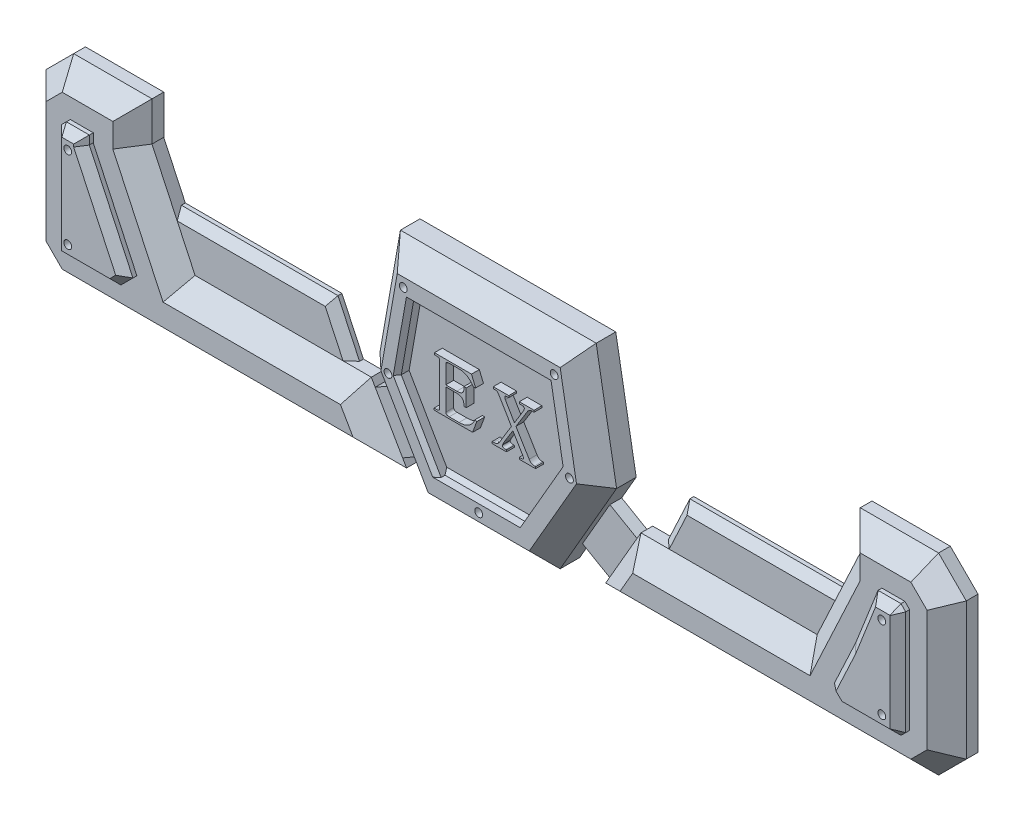
SolidWorks part; units mm, degrees
ref_plane "前视基准面" through (0, 0, 0) normal (0, 0, 1) x (1, 0, 0)
ref_plane "上视基准面" through (0, 0, 0) normal (0, 1, 0) x (1, 0, 0)
ref_plane "右视基准面" through (0, 0, 0) normal (1, 0, 0) x (0, 0, -1)
other "Configuration Table"
sketch "草图2" plane through (0, 0, 0) normal (0, 0, 1) x (1, 0, 0)
  line L0 (-21.0107, -24.9665) -> (10.5794, -24.9665)
  line L5 (10.5794, -24.9665) -> (24.9938, 0)
  line L6 (24.9938, 0) -> (19.7844, 29.5442)
  line L7 (19.7844, 29.5442) -> (-30.2156, 29.5442)
  line L8 (-30.2156, 29.5442) -> (-35.4251, 0)
  line L9 (-35.4251, 0) -> (-21.0107, -24.9665)
  dimension "D1" = 50
  dimension "D2" = 100
  dimension "D3" = 100
  dimension "D4" = 30
  dimension "D5" = 30
  dimension "D6" = 140
  dimension "D7" = 140
extrude "凸台-拉伸2" add sketch "草图2" along normal blind 10
chamfer "倒角1" distance 5 angle 45 6 edges at (-32.8203, 14.7721, 10) (-5.2156, 29.5442, 10) (22.3891, 14.7721, 10) (17.7866, -12.4832, 10) (-5.2156, -24.9665, 10) (-28.2179, -12.4832, 10)
sketch "草图4" plane through (0, 0, 10) normal (0, 0, 1) x (1, 0, 0)
  line L18 (-22.6637, 20.5442) -> (-25.993, 1.6631)
  line L19 (-25.993, 1.6631) -> (-15.8145, -15.9665)
  line L20 (-15.8145, -15.9665) -> (5.3833, -15.9665)
  line L21 (5.3833, -15.9665) -> (15.5617, 1.6631)
  line L22 (15.5617, 1.6631) -> (12.2325, 20.5442)
  line L23 (12.2325, 20.5442) -> (-22.6637, 20.5442)
  line L24 (-22.6637, 20.5442) -> (-25.993, 1.6631)
  line L25 (-25.993, 1.6631) -> (-15.8145, -15.9665)
  line L26 (-15.8145, -15.9665) -> (5.3833, -15.9665)
  line L27 (5.3833, -15.9665) -> (15.5617, 1.6631)
  line L28 (15.5617, 1.6631) -> (12.2325, 20.5442)
  line L29 (12.2325, 20.5442) -> (-22.6637, 20.5442)
  dimension "D1" = 4
extrude "切除-拉伸1" cut sketch "草图4" against normal blind 3
sketch "草图5" plane through (0, 0, 7) normal (0, 0, 1) x (1, 0, 0)
  text T0 "EX" font "宋体" height in points 42
extrude "凸台-拉伸3" add sketch "草图5" along normal blind 2
sketch "草图6" plane through (0, 0, 0) normal (0, 0, 1) x (1, 0, 0)
  line L1 (-35.4251, 0) -> (-21.0107, -24.9665) construction
  line L3 (-38.6461, -10.4211) -> (-31.7179, -6.4211)
  line L4 (-31.7179, -6.4211) -> (-24.7179, -18.5454)
  line L5 (-31.6461, -22.5454) -> (-38.6461, -10.4211)
  line L6 (-31.6461, -22.5454) -> (-24.7179, -18.5454)
  line L7 (-5.2156, 24.5442) -> (-5.2156, -15.9665) construction
  line L8 (15.5889, 24.5442) -> (-26.0201, 24.5442) construction
  line L9 (-15.8145, -15.9665) -> (5.3833, -15.9665) construction
  line L10 (-38.6461, -10.4211) -> (-31.7179, -6.4211)
  line L11 (-31.6461, -22.5454) -> (-24.7179, -18.5454)
  line L12 (-38.6461, -10.4211) -> (-31.7179, -6.4211)
  line L13 (-31.6461, -22.5454) -> (-24.7179, -18.5454)
  line L14 (-38.6461, -10.4211) -> (-31.7179, -6.4211)
  line L15 (-31.6461, -22.5454) -> (-24.7179, -18.5454)
  line L16 (-38.6461, -10.4211) -> (-31.7179, -6.4211)
  line L17 (-31.6461, -22.5454) -> (-24.7179, -18.5454)
  line L18 (-38.6461, -10.4211) -> (-31.7179, -6.4211)
  line L19 (-31.6461, -22.5454) -> (-24.7179, -18.5454)
  line L20 (-38.6461, -10.4211) -> (-31.7179, -6.4211)
  line L21 (-31.6461, -22.5454) -> (-24.7179, -18.5454)
  line L22 (-38.6461, -10.4211) -> (-31.7179, -6.4211)
  line L23 (-31.6461, -22.5454) -> (-24.7179, -18.5454)
  line L24 (-39.6457, -8.6896) -> (-38.6461, -10.4211)
  line L25 (-30.6461, -24.2775) -> (-31.6461, -22.5454)
  line L26 (-39.6457, -8.6896) -> (-84.6457, -8.6896)
  line L27 (-84.6457, -8.6896) -> (-95.6461, 14.8647)
  line L28 (-95.6461, 14.8647) -> (-95.6461, 24.8647)
  line L29 (-95.6461, 24.8647) -> (-115.6461, 24.8647)
  line L30 (-115.6461, 24.8647) -> (-122.7171, 17.7936)
  line L31 (-122.7171, 17.7936) -> (-122.7171, -17.2064)
  line L32 (-122.7171, -17.2064) -> (-115.6461, -24.2775)
  line L33 (-115.6461, -24.2775) -> (-30.6461, -24.2775)
  line L34 (-90.1459, 3.0875) -> (-50.1459, 3.0875)
  line L35 (-50.1459, 3.0875) -> (-44.6457, -8.6896)
  line L36 (39.7147, 3.0875) -> (34.2145, -8.6896)
  line L37 (79.7147, 3.0875) -> (39.7147, 3.0875)
  line L38 (105.2148, -24.2775) -> (20.2148, -24.2775)
  line L39 (112.2859, -17.2064) -> (105.2148, -24.2775)
  line L40 (112.2859, 17.7936) -> (112.2859, -17.2064)
  line L41 (105.2148, 24.8647) -> (112.2859, 17.7936)
  line L42 (85.2148, 24.8647) -> (105.2148, 24.8647)
  line L43 (85.2148, 14.8647) -> (85.2148, 24.8647)
  line L44 (74.2145, -8.6896) -> (85.2148, 14.8647)
  line L45 (29.2145, -8.6896) -> (74.2145, -8.6896)
  line L46 (20.2148, -24.2775) -> (21.2148, -22.5454)
  line L47 (29.2145, -8.6896) -> (28.2148, -10.4211)
  line L48 (21.2148, -22.5454) -> (14.2866, -18.5454)
  line L49 (28.2148, -10.4211) -> (21.2866, -6.4211)
  line L50 (21.2148, -22.5454) -> (14.2866, -18.5454)
  line L51 (28.2148, -10.4211) -> (21.2866, -6.4211)
  line L52 (21.2148, -22.5454) -> (14.2866, -18.5454)
  line L53 (28.2148, -10.4211) -> (21.2866, -6.4211)
  line L54 (21.2148, -22.5454) -> (14.2866, -18.5454)
  line L55 (28.2148, -10.4211) -> (21.2866, -6.4211)
  line L56 (21.2148, -22.5454) -> (14.2866, -18.5454)
  line L57 (28.2148, -10.4211) -> (21.2866, -6.4211)
  line L58 (21.2148, -22.5454) -> (14.2866, -18.5454)
  line L59 (28.2148, -10.4211) -> (21.2866, -6.4211)
  line L60 (21.2148, -22.5454) -> (14.2866, -18.5454)
  line L61 (28.2148, -10.4211) -> (21.2866, -6.4211)
  line L62 (21.2148, -22.5454) -> (14.2866, -18.5454)
  line L63 (21.2148, -22.5454) -> (28.2148, -10.4211)
  line L64 (21.2866, -6.4211) -> (14.2866, -18.5454)
  line L65 (28.2148, -10.4211) -> (21.2866, -6.4211)
  line L66 (-21.0107, -24.9665) -> (-35.4251, 0) construction
  point P40 (0, 0)
  dimension "D1" = 45
  dimension "D2" = 10
  dimension "D3" = 20
  dimension "D4" = 14
  dimension "D5" = 85
  dimension "D6" = 8
  dimension "D7" = 2
  dimension "D8" = 10
  dimension "D9" = 10
  dimension "D11" = 40
  dimension "D13" = 135
  dimension "D14" = 64.966
extrude "凸台-拉伸4" add sketch "草图6" along normal blind 3 contours L5 L6 L3 | L49 L64 L48 L63 region at (-31.682, -14.4832, 0) region at (21.2507, -14.4832, 0)
extrude "凸台-拉伸5" add sketch "草图6<4>" along normal blind 8 contours L32 L33 L25 L5 L24 L26 L27 L28 L29 L30 L31 | L63 L46 L38 L39 L40 L41 L42 L43 L44 L45 L47 region at (-90.4252, -6.5705, 0) region at (79.9939, -6.5705, 0)
sketch "草图6<4>" plane through (0, 0, 0) normal (0, 0, 1) x (1, 0, 0) same geometry as "草图6"
extrude "凸台-拉伸6" add sketch "草图6<5>" along normal blind 3 contours L34 L27 L26 | L36 L45 L44 L37 region at (-67.3958, -2.801, 0) region at (56.9646, -2.801, 0)
sketch "草图6<5>" plane through (0, 0, 0) normal (0, 0, 1) x (1, 0, 0) same geometry as "草图6"
chamfer "倒角2" distance 2 angle 45 4 edges at (-70.1459, 3.0875, 3) (59.7147, 3.0875, 3) (36.9646, -2.801, 3) (-47.3958, -2.801, 3)
chamfer "倒角4" distance 5 angle 45 18 edges at (-122.7171, 0.2936, 8) (-119.1816, 21.3291, 8) (-105.6461, 24.8647, 8) (-95.6461, 19.8647, 8) (-90.1459, 3.0875, 8) (-62.1457, -8.6896, 8) (-35.1459, -16.4835, 8) (-73.1461, -24.2775, 8) (-119.1816, -20.7419, 8) (51.7145, -8.6896, 8) (79.7147, 3.0875, 8) (85.2148, 19.8647, 8) (95.2148, 24.8647, 8) (108.7504, 21.3291, 8) (112.2859, 0.2936, 8) (108.7504, -20.7419, 8) (62.7148, -24.2775, 8) (24.7147, -16.4835, 8)
sketch "草图10" plane through (0, 0, 8) normal (0, 0, 1) x (1, 0, 0)
  line L10 (-94.5126, -11.1946) -> (-97.5954, -14.2775)
  line L12 (-4.9424, -14.2775) -> (-4.9424, 26.4661) construction
  line L13 (95.7612, 14.8647) -> (101.619, 14.8647)
  line L14 (90.1151, 0.5551) -> (95.7612, 14.8647)
  line L15 (84.6277, -11.1946) -> (90.1151, 0.5551)
  line L16 (101.619, -14.2775) -> (87.7105, -14.2775)
  line L17 (102.8322, -13.0643) -> (101.619, -14.2775)
  line L18 (102.8322, 13.6515) -> (102.8322, -13.0643)
  line L19 (-111.5039, 14.8647) -> (-112.7171, 13.6515)
  line L22 (-111.5039, -14.2775) -> (-93.0729, -14.2775)
  line L23 (-93.0729, -14.2775) -> (-105.6461, 12.6446)
  line L29 (-111.5039, -14.2775) -> (-97.5954, -14.2775)
  line L30 (-94.5126, -11.1946) -> (-105.6461, 12.6446)
  line L33 (101.619, 14.8647) -> (102.8322, 13.6515)
  line L34 (84.6277, -11.1946) -> (87.7105, -14.2775)
  line L41 (-111.5039, 14.8647) -> (-112.7171, 13.6515)
  line L45 (-112.7171, 13.6515) -> (-112.7171, -13.0643)
  line L47 (-112.7171, 13.6515) -> (-112.7171, -13.0643)
  line L48 (-112.7171, -13.0643) -> (-111.5039, -14.2775)
  line L49 (-112.7171, -13.0643) -> (-111.5039, -14.2775)
  line L50 (-105.6461, 12.6446) -> (-105.6461, 14.8647)
  line L51 (-105.6461, 12.6446) -> (-105.6461, 14.8647)
  line L52 (-105.6461, 14.8647) -> (-111.5039, 14.8647)
  line L53 (-105.6461, 14.8647) -> (-111.5039, 14.8647)
  dimension "D1" = 5
extrude "凸台-拉伸7" add sketch "草图10" along normal blind 3
chamfer "倒角5" distance 2 angle 45 16 edges at (98.6901, 14.8647, 11) (102.2256, 14.2581, 11) (102.8322, 0.2936, 11) (102.2256, -13.6709, 11) (94.6648, -14.2775, 11) (86.1691, -12.7361, 11) (87.3714, -5.3198, 11) (92.9381, 7.7099, 11) (-96.054, -12.7361, 11) (-104.5497, -14.2775, 11) (-112.1105, -13.6709, 11) (-112.7171, 0.2936, 11) (-112.1105, 14.2581, 11) (-108.575, 14.8647, 11) (-105.6461, 13.7547, 11) (-100.0793, 0.725, 11)
chamfer "倒角6" distance 1 angle 45 6 edges at (-5.2156, -15.9665, 7) (10.4725, -7.1517, 7) (13.8971, 11.1037, 10) (-5.2156, 20.5442, 7) (-24.3283, 11.1037, 10) (-20.9037, -7.1517, 10)
sketch "草图11" plane through (0, 0, 11) normal (0, 0, 1) x (1, 0, 0)
  line L0 (-5.2156, 20.5442) -> (-5.2156, 0) construction
  line L1 (13.2479, 20.5442) -> (-23.6791, 20.5442) construction
  circle A0 centre (-109.1608, 10.7846) radius 1
  circle A1 centre (-109.1608, -10.1386) radius 1
  circle A2 centre (98.7296, -10.1386) radius 1
  circle A3 centre (98.7296, 10.7846) radius 1
extrude "切除-拉伸2" cut sketch "草图11" against normal through all
sketch "草图12" plane through (0, 0, 10) normal (0, 0, 1) x (1, 0, 0)
  line L1 (-5.2156, 20.5442) -> (-5.2156, 9.929) construction
  line L2 (-22.6637, 20.5442) -> (12.2325, 20.5442) construction
  circle A0 centre (-24.4837, 22.2402) radius 1
  circle A1 centre (-28.3894, 1.2686) radius 1
  circle A2 centre (-5.2156, -17.9531) radius 1
  circle A3 centre (17.9582, 1.2686) radius 1
  circle A4 centre (14.0525, 22.2402) radius 1
extrude "切除-拉伸3" cut sketch "草图12" against normal through all
